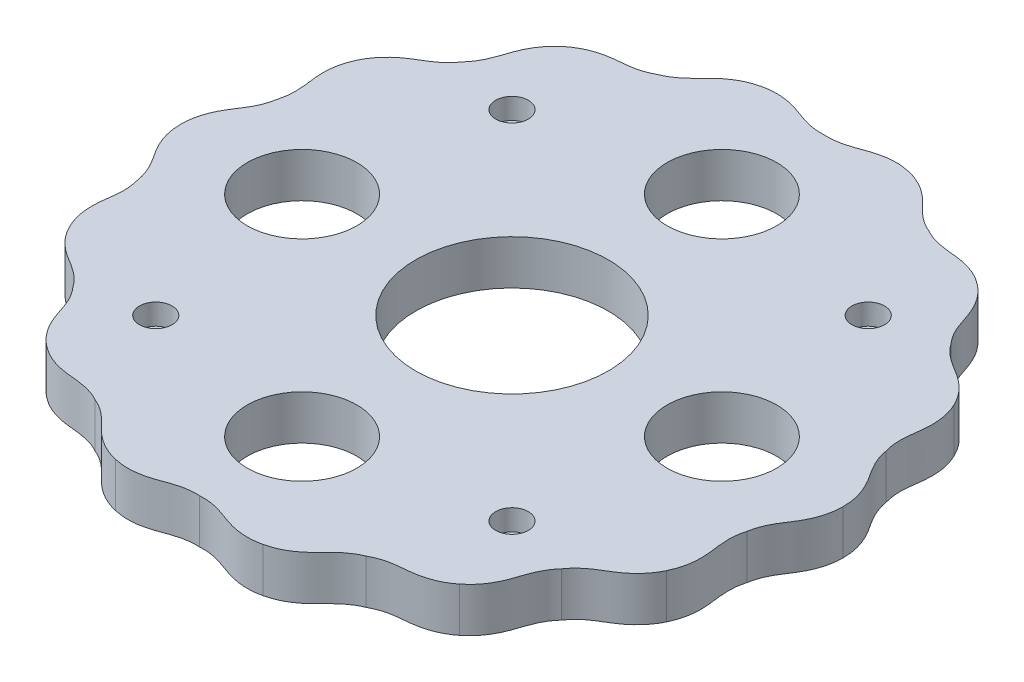
SolidWorks part; units mm, degrees
ref_plane "Front Plane" through (0, 0, 0) normal (0, 0, 1) x (1, 0, 0)
ref_plane "Top Plane" through (0, 0, 0) normal (0, 1, 0) x (1, 0, 0)
ref_plane "Right Plane" through (0, 0, 0) normal (1, 0, 0) x (0, 0, -1)
sketch "Sketch1" plane through (0, 0, 0) normal (0, 1, 0) x (1, 0, 0)
  line L0 (0, 0) -> (37.5, 0) construction
  line L1 (0, 0) -> (37.4807, 1.2019) construction
  line L2 (0, 0) -> (37.423, 2.4026) construction
  line L3 (0, 0) -> (37.3267, 3.6009) construction
  line L4 (0, 0) -> (37.1921, 4.7954) construction
  line L5 (0, 0) -> (37.0193, 5.985) construction
  line L6 (0, 0) -> (36.8085, 7.1684) construction
  line L7 (0, 0) -> (36.5598, 8.3445) construction
  line L8 (0, 0) -> (36.2736, 9.512) construction
  line L9 (0, 0) -> (35.95, 10.6698) construction
  line L10 (0, 0) -> (35.5896, 11.8166) construction
  line L11 (0, 0) -> (35.1926, 12.9512) construction
  line L12 (0, 0) -> (34.7594, 14.0725) construction
  line L13 (0, 0) -> (34.2905, 15.1794) construction
  line L14 (0, 0) -> (33.7863, 16.2706) construction
  line L15 (37.5, 0) -> (38.5, 0) construction
  line L16 (37.4807, 1.2019) -> (38.3521, 1.6927) construction
  line L17 (37.423, 2.4026) -> (37.9413, 3.2578) construction
  line L18 (37.3267, 3.6009) -> (37.3588, 4.6003) construction
  line L19 (37.1921, 4.7954) -> (36.7296, 5.682) construction
  line L20 (37.0193, 5.985) -> (36.1812, 6.5305) construction
  line L21 (36.8085, 7.1684) -> (35.8105, 7.2325) construction
  line L22 (36.5598, 8.3445) -> (35.5849, 8.122) construction
  line L23 (37, 0.0019) -> (37, 0)
  line L24 (33.3367, 16.052) -> (33.3358, 16.0537)
  line L25 (37, -0.0019) -> (37, 0)
  line L26 (33.3367, -16.052) -> (33.3358, -16.0537)
  line L27 (33.335, -16.0554) -> (33.3358, -16.0537)
  line L28 (23.0706, -28.9266) -> (23.0691, -28.9278)
  line L29 (23.0677, -28.9289) -> (23.0691, -28.9278)
  line L30 (8.2351, -36.0719) -> (8.2333, -36.0723)
  line L31 (8.2315, -36.0727) -> (8.2333, -36.0723)
  line L32 (-8.2315, -36.0727) -> (-8.2333, -36.0723)
  line L33 (-8.2351, -36.0719) -> (-8.2333, -36.0723)
  line L34 (-23.0677, -28.9289) -> (-23.0691, -28.9278)
  line L35 (-23.0706, -28.9266) -> (-23.0691, -28.9278)
  line L36 (-33.335, -16.0554) -> (-33.3358, -16.0537)
  line L37 (-33.3367, -16.052) -> (-33.3358, -16.0537)
  line L38 (-37, -0.0019) -> (-37, 0)
  line L39 (-37, 0.0019) -> (-37, 0)
  line L40 (-33.3367, 16.052) -> (-33.3358, 16.0537)
  line L41 (-33.335, 16.0554) -> (-33.3358, 16.0537)
  line L42 (-23.0706, 28.9266) -> (-23.0691, 28.9278)
  line L43 (-23.0677, 28.9289) -> (-23.0691, 28.9278)
  line L44 (-8.2351, 36.0719) -> (-8.2333, 36.0723)
  line L45 (-8.2315, 36.0727) -> (-8.2333, 36.0723)
  line L46 (8.2315, 36.0727) -> (8.2333, 36.0723)
  line L47 (8.2351, 36.0719) -> (8.2333, 36.0723)
  line L48 (23.0677, 28.9289) -> (23.0691, 28.9278)
  line L49 (23.0706, 28.9266) -> (23.0691, 28.9278)
  line L50 (33.335, 16.0554) -> (33.3358, 16.0537)
  line L51 (35.5, 0.0037) -> (35.5, 0)
  line L52 (31.986, 15.3995) -> (31.9844, 15.4029)
  line L53 (35.5, -0.0037) -> (35.5, 0)
  line L54 (31.986, -15.3995) -> (31.9844, -15.4029)
  line L55 (31.9828, -15.4062) -> (31.9844, -15.4029)
  line L56 (22.1368, -27.7527) -> (22.1339, -27.755)
  line L57 (22.131, -27.7573) -> (22.1339, -27.755)
  line L58 (7.9031, -34.6091) -> (7.8995, -34.6099)
  line L59 (7.8959, -34.6108) -> (7.8995, -34.6099)
  line L60 (-7.8959, -34.6108) -> (-7.8995, -34.6099)
  line L61 (-7.9031, -34.6091) -> (-7.8995, -34.6099)
  line L62 (-22.131, -27.7573) -> (-22.1339, -27.755)
  line L63 (-22.1368, -27.7527) -> (-22.1339, -27.755)
  line L64 (-31.9828, -15.4062) -> (-31.9844, -15.4029)
  line L65 (-31.986, -15.3995) -> (-31.9844, -15.4029)
  line L66 (-35.5, -0.0037) -> (-35.5, 0)
  line L67 (-35.5, 0.0037) -> (-35.5, 0)
  line L68 (-31.986, 15.3995) -> (-31.9844, 15.4029)
  line L69 (-31.9828, 15.4062) -> (-31.9844, 15.4029)
  line L70 (-22.1368, 27.7527) -> (-22.1339, 27.755)
  line L71 (-22.131, 27.7573) -> (-22.1339, 27.755)
  line L72 (-7.9031, 34.6091) -> (-7.8995, 34.6099)
  line L73 (-7.8959, 34.6108) -> (-7.8995, 34.6099)
  line L74 (7.8959, 34.6108) -> (7.8995, 34.6099)
  line L75 (7.9031, 34.6091) -> (7.8995, 34.6099)
  line L76 (22.131, 27.7573) -> (22.1339, 27.755)
  line L77 (22.1368, 27.7527) -> (22.1339, 27.755)
  line L78 (31.9828, 15.4062) -> (31.9844, 15.4029)
  circle A0 centre (0, 0) radius 35 construction
  circle A1 centre (37.5, 0) radius 2.5 construction
  circle A2 centre (0, 0) radius 37.5 construction
  spline S0 degree 3 poles (35.5849, 8.122) (35.6266, 7.5364) (36.0345, 6.7125) (36.7836, 5.6218) (37.4152, 4.5501) (38.2239, 2.702) (38.5014, 1.1074) (38.5, 0) knots 0 0 0 0 0.195516 0.310928 0.453873 0.621058 1 1 1 1
  spline S1 degree 3 poles (35.5849, 8.122) (35.3683, 8.6678) (35.3784, 9.5871) (35.5801, 10.8948) (35.6841, 12.1344) (35.611, 14.1503) (35.169, 15.7074) (34.6873, 16.7045) knots 0 0 0 0 0.195516 0.310928 0.453873 0.621058 1 1 1 1
  spline S2 degree 1 poles (34.1119, 7.7858) (33.3367, 16.052) knots 0 0 1 1 construction
  spline S3 degree 1 poles (34.1119, 7.7858) (37, 0.0019) knots 0 0 1 1 construction
  spline S4 degree 3 poles (33.3367, 16.052) (33.6005, 15.5058) (33.9037, 14.6401) (34.1146, 13.4372) (34.174, 12.5211) (34.1413, 11.5771) (34.0239, 10.6392) (33.8823, 9.6155) (33.9055, 8.625) (34.0243, 8.0514) (34.1119, 7.7858) knots 0.015853 0.015853 0.015853 0.015853 0.26189 0.384908 0.507927 0.630945 0.753963 0.876982 0.938491 1 1 1 1
  spline S5 degree 3 poles (34.1119, 7.7858) (34.1483, 7.5085) (34.2901, 6.9402) (34.6989, 6.0377) (35.2706, 5.1769) (35.7834, 4.3828) (36.2224, 3.5464) (36.5664, 2.6953) (36.8983, 1.52) (37.0008, 0.6085) (37, 0.0019) knots 0.015853 0.015853 0.015853 0.015853 0.077362 0.138872 0.26189 0.384908 0.507927 0.630945 0.753963 1 1 1 1
  spline S6 degree 3 poles (37, -0.0019) (37.0008, -0.6085) (36.8983, -1.52) (36.5664, -2.6953) (36.2224, -3.5464) (35.7834, -4.3828) (35.2706, -5.1769) (34.6989, -6.0377) (34.2901, -6.9402) (34.1483, -7.5085) (34.1119, -7.7858) knots 0.015853 0.015853 0.015853 0.015853 0.26189 0.384908 0.507927 0.630945 0.753963 0.876982 0.938491 1 1 1 1
  spline S7 degree 3 poles (34.1119, -7.7858) (34.0243, -8.0514) (33.9055, -8.625) (33.8823, -9.6155) (34.0239, -10.6392) (34.1413, -11.5771) (34.174, -12.5211) (34.1146, -13.4372) (33.9037, -14.6401) (33.6005, -15.5058) (33.3367, -16.052) knots 0.015853 0.015853 0.015853 0.015853 0.077362 0.138872 0.26189 0.384908 0.507927 0.630945 0.753963 1 1 1 1
  spline S8 degree 3 poles (33.335, -16.0554) (33.0725, -16.6022) (32.5847, -17.3791) (31.7758, -18.2939) (31.0965, -18.9115) (30.3381, -19.4746) (29.5316, -19.9675) (28.6429, -20.4951) (27.8831, -21.1308) (27.5087, -21.5813) (27.3556, -21.8154) knots 0.015853 0.015853 0.015853 0.015853 0.26189 0.384908 0.507927 0.630945 0.753963 0.876982 0.938491 1 1 1 1
  spline S9 degree 3 poles (27.3556, -21.8154) (27.1615, -22.0167) (26.8056, -22.4819) (26.3549, -23.3642) (26.0383, -24.348) (25.7371, -25.2439) (25.357, -26.1087) (24.906, -26.9083) (24.1941, -27.9005) (23.5453, -28.549) (23.0706, -28.9266) knots 0.015853 0.015853 0.015853 0.015853 0.077362 0.138872 0.26189 0.384908 0.507927 0.630945 0.753963 1 1 1 1
  spline S10 degree 3 poles (23.0677, -28.9289) (22.5939, -29.3077) (21.8173, -29.796) (20.6915, -30.2693) (19.8116, -30.531) (18.884, -30.7092) (17.9435, -30.8034) (16.9139, -30.8931) (15.9535, -31.1362) (15.4207, -31.3797) (15.1812, -31.5241) knots 0.015853 0.015853 0.015853 0.015853 0.26189 0.384908 0.507927 0.630945 0.753963 0.876982 0.938491 1 1 1 1
  spline S11 degree 3 poles (15.1812, -31.5241) (14.919, -31.6213) (14.3964, -31.886) (13.6076, -32.4854) (12.8955, -33.2344) (12.2354, -33.9109) (11.5177, -34.5251) (10.7645, -35.0499) (9.6926, -35.6349) (8.8266, -35.9377) (8.2351, -36.0719) knots 0.015853 0.015853 0.015853 0.015853 0.077362 0.138872 0.26189 0.384908 0.507927 0.630945 0.753963 1 1 1 1
  spline S12 degree 3 poles (8.2315, -36.0727) (7.6402, -36.2085) (6.7287, -36.3114) (5.5091, -36.2494) (4.6028, -36.1034) (3.6897, -35.8614) (2.8014, -35.5383) (1.8349, -35.1724) (0.8641, -34.9747) (0.2785, -34.9629) (0, -34.9891) knots 0.015853 0.015853 0.015853 0.015853 0.26189 0.384908 0.507927 0.630945 0.753963 0.876982 0.938491 1 1 1 1
  spline S13 degree 3 poles (0, -34.9891) (-0.2785, -34.9629) (-0.8641, -34.9747) (-1.8349, -35.1724) (-2.8014, -35.5383) (-3.6897, -35.8614) (-4.6028, -36.1034) (-5.5091, -36.2494) (-6.7287, -36.3114) (-7.6402, -36.2085) (-8.2315, -36.0727) knots 0.015853 0.015853 0.015853 0.015853 0.077362 0.138872 0.26189 0.384908 0.507927 0.630945 0.753963 1 1 1 1
  spline S14 degree 3 poles (-8.2351, -36.0719) (-8.8266, -35.9377) (-9.6926, -35.6349) (-10.7645, -35.0499) (-11.5177, -34.5251) (-12.2354, -33.9109) (-12.8955, -33.2344) (-13.6076, -32.4854) (-14.3964, -31.886) (-14.919, -31.6213) (-15.1812, -31.5241) knots 0.015853 0.015853 0.015853 0.015853 0.26189 0.384908 0.507927 0.630945 0.753963 0.876982 0.938491 1 1 1 1
  spline S15 degree 3 poles (-15.1812, -31.5241) (-15.4207, -31.3797) (-15.9535, -31.1362) (-16.9139, -30.8931) (-17.9435, -30.8034) (-18.884, -30.7092) (-19.8116, -30.531) (-20.6915, -30.2693) (-21.8173, -29.796) (-22.5939, -29.3077) (-23.0677, -28.9289) knots 0.015853 0.015853 0.015853 0.015853 0.077362 0.138872 0.26189 0.384908 0.507927 0.630945 0.753963 1 1 1 1
  spline S16 degree 3 poles (-23.0706, -28.9266) (-23.5453, -28.549) (-24.1941, -27.9005) (-24.906, -26.9083) (-25.357, -26.1087) (-25.7371, -25.2439) (-26.0383, -24.348) (-26.3549, -23.3642) (-26.8056, -22.4819) (-27.1615, -22.0167) (-27.3556, -21.8154) knots 0.015853 0.015853 0.015853 0.015853 0.26189 0.384908 0.507927 0.630945 0.753963 0.876982 0.938491 1 1 1 1
  spline S17 degree 3 poles (-27.3556, -21.8154) (-27.5087, -21.5813) (-27.8831, -21.1308) (-28.6429, -20.4951) (-29.5316, -19.9675) (-30.3381, -19.4746) (-31.0965, -18.9115) (-31.7758, -18.2939) (-32.5847, -17.3791) (-33.0725, -16.6022) (-33.335, -16.0554) knots 0.015853 0.015853 0.015853 0.015853 0.077362 0.138872 0.26189 0.384908 0.507927 0.630945 0.753963 1 1 1 1
  spline S18 degree 3 poles (-33.3367, -16.052) (-33.6005, -15.5058) (-33.9037, -14.6401) (-34.1146, -13.4372) (-34.174, -12.5211) (-34.1413, -11.5771) (-34.0239, -10.6392) (-33.8823, -9.6155) (-33.9055, -8.625) (-34.0243, -8.0514) (-34.1119, -7.7858) knots 0.015853 0.015853 0.015853 0.015853 0.26189 0.384908 0.507927 0.630945 0.753963 0.876982 0.938491 1 1 1 1
  spline S19 degree 3 poles (-34.1119, -7.7858) (-34.1483, -7.5085) (-34.2901, -6.9402) (-34.6989, -6.0377) (-35.2706, -5.1769) (-35.7834, -4.3828) (-36.2224, -3.5464) (-36.5664, -2.6953) (-36.8983, -1.52) (-37.0008, -0.6085) (-37, -0.0019) knots 0.015853 0.015853 0.015853 0.015853 0.077362 0.138872 0.26189 0.384908 0.507927 0.630945 0.753963 1 1 1 1
  spline S20 degree 3 poles (-37, 0.0019) (-37.0008, 0.6085) (-36.8983, 1.52) (-36.5664, 2.6953) (-36.2224, 3.5464) (-35.7834, 4.3828) (-35.2706, 5.1769) (-34.6989, 6.0377) (-34.2901, 6.9402) (-34.1483, 7.5085) (-34.1119, 7.7858) knots 0.015853 0.015853 0.015853 0.015853 0.26189 0.384908 0.507927 0.630945 0.753963 0.876982 0.938491 1 1 1 1
  spline S21 degree 3 poles (-34.1119, 7.7858) (-34.0243, 8.0514) (-33.9055, 8.625) (-33.8823, 9.6155) (-34.0239, 10.6392) (-34.1413, 11.5771) (-34.174, 12.5211) (-34.1146, 13.4372) (-33.9037, 14.6401) (-33.6005, 15.5058) (-33.3367, 16.052) knots 0.015853 0.015853 0.015853 0.015853 0.077362 0.138872 0.26189 0.384908 0.507927 0.630945 0.753963 1 1 1 1
  spline S22 degree 3 poles (-33.335, 16.0554) (-33.0725, 16.6022) (-32.5847, 17.3791) (-31.7758, 18.2939) (-31.0965, 18.9115) (-30.3381, 19.4746) (-29.5316, 19.9675) (-28.6429, 20.4951) (-27.8831, 21.1308) (-27.5087, 21.5813) (-27.3556, 21.8154) knots 0.015853 0.015853 0.015853 0.015853 0.26189 0.384908 0.507927 0.630945 0.753963 0.876982 0.938491 1 1 1 1
  spline S23 degree 3 poles (-27.3556, 21.8154) (-27.1615, 22.0167) (-26.8056, 22.4819) (-26.3549, 23.3642) (-26.0383, 24.348) (-25.7371, 25.2439) (-25.357, 26.1087) (-24.906, 26.9083) (-24.1941, 27.9005) (-23.5453, 28.549) (-23.0706, 28.9266) knots 0.015853 0.015853 0.015853 0.015853 0.077362 0.138872 0.26189 0.384908 0.507927 0.630945 0.753963 1 1 1 1
  spline S24 degree 3 poles (-23.0677, 28.9289) (-22.5939, 29.3077) (-21.8173, 29.796) (-20.6915, 30.2693) (-19.8116, 30.531) (-18.884, 30.7092) (-17.9435, 30.8034) (-16.9139, 30.8931) (-15.9535, 31.1362) (-15.4207, 31.3797) (-15.1812, 31.5241) knots 0.015853 0.015853 0.015853 0.015853 0.26189 0.384908 0.507927 0.630945 0.753963 0.876982 0.938491 1 1 1 1
  spline S25 degree 3 poles (-15.1812, 31.5241) (-14.919, 31.6213) (-14.3964, 31.886) (-13.6076, 32.4854) (-12.8955, 33.2344) (-12.2354, 33.9109) (-11.5177, 34.5251) (-10.7645, 35.0499) (-9.6926, 35.6349) (-8.8266, 35.9377) (-8.2351, 36.0719) knots 0.015853 0.015853 0.015853 0.015853 0.077362 0.138872 0.26189 0.384908 0.507927 0.630945 0.753963 1 1 1 1
  spline S26 degree 3 poles (-8.2315, 36.0727) (-7.6402, 36.2085) (-6.7287, 36.3114) (-5.5091, 36.2494) (-4.6028, 36.1034) (-3.6897, 35.8614) (-2.8014, 35.5383) (-1.8349, 35.1724) (-0.8641, 34.9747) (-0.2785, 34.9629) (0, 34.9891) knots 0.015853 0.015853 0.015853 0.015853 0.26189 0.384908 0.507927 0.630945 0.753963 0.876982 0.938491 1 1 1 1
  spline S27 degree 3 poles (0, 34.9891) (0.2785, 34.9629) (0.8641, 34.9747) (1.8349, 35.1724) (2.8014, 35.5383) (3.6897, 35.8614) (4.6028, 36.1034) (5.5091, 36.2494) (6.7287, 36.3114) (7.6402, 36.2085) (8.2315, 36.0727) knots 0.015853 0.015853 0.015853 0.015853 0.077362 0.138872 0.26189 0.384908 0.507927 0.630945 0.753963 1 1 1 1
  spline S28 degree 3 poles (8.2351, 36.0719) (8.8266, 35.9377) (9.6926, 35.6349) (10.7645, 35.0499) (11.5177, 34.5251) (12.2354, 33.9109) (12.8955, 33.2344) (13.6076, 32.4854) (14.3964, 31.886) (14.919, 31.6213) (15.1812, 31.5241) knots 0.015853 0.015853 0.015853 0.015853 0.26189 0.384908 0.507927 0.630945 0.753963 0.876982 0.938491 1 1 1 1
  spline S29 degree 3 poles (15.1812, 31.5241) (15.4207, 31.3797) (15.9535, 31.1362) (16.9139, 30.8931) (17.9435, 30.8034) (18.884, 30.7092) (19.8116, 30.531) (20.6915, 30.2693) (21.8173, 29.796) (22.5939, 29.3077) (23.0677, 28.9289) knots 0.015853 0.015853 0.015853 0.015853 0.077362 0.138872 0.26189 0.384908 0.507927 0.630945 0.753963 1 1 1 1
  spline S30 degree 3 poles (23.0706, 28.9266) (23.5453, 28.549) (24.1941, 27.9005) (24.906, 26.9083) (25.357, 26.1087) (25.7371, 25.2439) (26.0383, 24.348) (26.3549, 23.3642) (26.8056, 22.4819) (27.1615, 22.0167) (27.3556, 21.8154) knots 0.015853 0.015853 0.015853 0.015853 0.26189 0.384908 0.507927 0.630945 0.753963 0.876982 0.938491 1 1 1 1
  spline S31 degree 3 poles (27.3556, 21.8154) (27.5087, 21.5813) (27.8831, 21.1308) (28.6429, 20.4951) (29.5316, 19.9675) (30.3381, 19.4746) (31.0965, 18.9115) (31.7758, 18.2939) (32.5847, 17.3791) (33.0725, 16.6022) (33.335, 16.0554) knots 0.015853 0.015853 0.015853 0.015853 0.077362 0.138872 0.26189 0.384908 0.507927 0.630945 0.753963 1 1 1 1
  spline S32 degree 1 poles (32.6448, 7.451) (35.5, 0.0037) knots 0 0 1 1 construction
  spline S33 degree 1 poles (32.6448, 7.451) (31.986, 15.3995) knots 0 0 1 1 construction
  spline S34 degree 3 poles (35.5, 0.0037) (35.5006, 0.4959) (35.4183, 1.2336) (35.1496, 2.1927) (34.8707, 2.8896) (34.4997, 3.6015) (34.1394, 4.1652) (33.6939, 4.8394) (33.3068, 5.4873) (32.9751, 6.1975) (32.758, 6.8733) (32.6748, 7.2607) (32.6448, 7.451) knots 0.023011 0.023011 0.023011 0.023011 0.267258 0.389382 0.511505 0.633629 0.755753 0.816814 0.877876 0.938938 0.969469 1 1 1 1
  spline S35 degree 3 poles (32.6448, 7.451) (32.5893, 7.6354) (32.4961, 8.0206) (32.3985, 8.7236) (32.3893, 9.5074) (32.4569, 10.2591) (32.5657, 11.0598) (32.6458, 11.724) (32.6712, 12.5264) (32.6201, 13.2752) (32.446, 14.256) (32.2001, 14.9563) (31.986, 15.3995) knots 0.023011 0.023011 0.023011 0.023011 0.053542 0.084072 0.145134 0.206196 0.267258 0.389382 0.511505 0.633629 0.755753 1 1 1 1
  spline S36 degree 3 poles (32.6448, -7.451) (32.6748, -7.2607) (32.758, -6.8733) (32.9751, -6.1975) (33.3068, -5.4873) (33.6939, -4.8394) (34.1394, -4.1652) (34.4997, -3.6015) (34.8707, -2.8896) (35.1496, -2.1927) (35.4183, -1.2336) (35.5006, -0.4959) (35.5, -0.0037) knots 0.023011 0.023011 0.023011 0.023011 0.053542 0.084072 0.145134 0.206196 0.267258 0.389382 0.511505 0.633629 0.755753 1 1 1 1
  spline S37 degree 3 poles (31.986, -15.3995) (32.2001, -14.9563) (32.446, -14.256) (32.6201, -13.2752) (32.6712, -12.5264) (32.6458, -11.724) (32.5657, -11.0598) (32.4569, -10.2591) (32.3893, -9.5074) (32.3985, -8.7236) (32.4961, -8.0206) (32.5893, -7.6354) (32.6448, -7.451) knots 0.023011 0.023011 0.023011 0.023011 0.267258 0.389382 0.511505 0.633629 0.755753 0.816814 0.877876 0.938938 0.969469 1 1 1 1
  spline S38 degree 3 poles (26.1791, -20.8771) (26.2887, -20.7187) (26.5317, -20.4057) (27.0205, -19.8911) (27.6275, -19.3952) (28.2574, -18.9793) (28.9513, -18.5652) (29.5206, -18.2137) (30.1637, -17.7333) (30.7173, -17.2264) (31.3755, -16.4789) (31.7698, -15.8499) (31.9828, -15.4062) knots 0.023011 0.023011 0.023011 0.023011 0.053542 0.084072 0.145134 0.206196 0.267258 0.389382 0.511505 0.633629 0.755753 1 1 1 1
  spline S39 degree 3 poles (22.1368, -27.7527) (22.522, -27.4463) (23.0474, -26.922) (23.6297, -26.1139) (24.0007, -25.4614) (24.326, -24.7275) (24.542, -24.0943) (24.7914, -23.3257) (25.0566, -22.619) (25.405, -21.9169) (25.798, -21.3258) (26.0491, -21.0192) (26.1791, -20.8771) knots 0.023011 0.023011 0.023011 0.023011 0.267258 0.389382 0.511505 0.633629 0.755753 0.816814 0.877876 0.938938 0.969469 1 1 1 1
  spline S40 degree 3 poles (14.5283, -30.1683) (14.6957, -30.0732) (15.0505, -29.8966) (15.7143, -29.645) (16.4763, -29.4616) (17.2242, -29.3602) (18.0291, -29.2882) (18.6945, -29.2185) (19.4823, -29.0647) (20.201, -28.8482) (21.1184, -28.4603) (21.7465, -28.0647) (22.131, -27.7573) knots 0.023011 0.023011 0.023011 0.023011 0.053542 0.084072 0.145134 0.206196 0.267258 0.389382 0.511505 0.633629 0.755753 1 1 1 1
  spline S41 degree 3 poles (7.9031, -34.6091) (8.3831, -34.5002) (9.084, -34.2557) (9.9593, -33.7804) (10.5766, -33.3534) (11.1881, -32.8334) (11.6575, -32.3566) (12.2156, -31.7723) (12.7612, -31.2507) (13.3797, -30.7693) (13.9903, -30.4072) (14.3495, -30.2399) (14.5283, -30.1683) knots 0.023011 0.023011 0.023011 0.023011 0.267258 0.389382 0.511505 0.633629 0.755753 0.816814 0.877876 0.938938 0.969469 1 1 1 1
  spline S42 degree 3 poles (0, -33.4843) (0.1922, -33.4712) (0.5884, -33.4661) (1.2956, -33.5274) (2.0617, -33.6928) (2.7796, -33.926) (3.536, -34.2103) (4.1657, -34.4362) (4.9423, -34.6394) (5.6838, -34.7562) (6.6786, -34.8048) (7.4161, -34.7209) (7.8959, -34.6108) knots 0.023011 0.023011 0.023011 0.023011 0.053542 0.084072 0.145134 0.206196 0.267258 0.389382 0.511505 0.633629 0.755753 1 1 1 1
  spline S43 degree 3 poles (-7.8959, -34.6108) (-7.4161, -34.7209) (-6.6786, -34.8048) (-5.6838, -34.7562) (-4.9423, -34.6394) (-4.1657, -34.4362) (-3.536, -34.2103) (-2.7796, -33.926) (-2.0617, -33.6928) (-1.2956, -33.5274) (-0.5884, -33.4661) (-0.1922, -33.4712) (0, -33.4843) knots 0.023011 0.023011 0.023011 0.023011 0.267258 0.389382 0.511505 0.633629 0.755753 0.816814 0.877876 0.938938 0.969469 1 1 1 1
  spline S44 degree 3 poles (-14.5283, -30.1683) (-14.3495, -30.2399) (-13.9903, -30.4072) (-13.3797, -30.7693) (-12.7612, -31.2507) (-12.2156, -31.7723) (-11.6575, -32.3566) (-11.1881, -32.8334) (-10.5766, -33.3534) (-9.9593, -33.7804) (-9.084, -34.2557) (-8.3831, -34.5002) (-7.9031, -34.6091) knots 0.023011 0.023011 0.023011 0.023011 0.053542 0.084072 0.145134 0.206196 0.267258 0.389382 0.511505 0.633629 0.755753 1 1 1 1
  spline S45 degree 3 poles (-22.131, -27.7573) (-21.7465, -28.0647) (-21.1184, -28.4603) (-20.201, -28.8482) (-19.4823, -29.0647) (-18.6945, -29.2185) (-18.0291, -29.2882) (-17.2242, -29.3602) (-16.4763, -29.4616) (-15.7143, -29.645) (-15.0505, -29.8966) (-14.6957, -30.0732) (-14.5283, -30.1683) knots 0.023011 0.023011 0.023011 0.023011 0.267258 0.389382 0.511505 0.633629 0.755753 0.816814 0.877876 0.938938 0.969469 1 1 1 1
  spline S46 degree 3 poles (-26.1791, -20.8771) (-26.0491, -21.0192) (-25.798, -21.3258) (-25.405, -21.9169) (-25.0566, -22.619) (-24.7914, -23.3257) (-24.542, -24.0943) (-24.326, -24.7275) (-24.0007, -25.4614) (-23.6297, -26.1139) (-23.0474, -26.922) (-22.522, -27.4463) (-22.1368, -27.7527) knots 0.023011 0.023011 0.023011 0.023011 0.053542 0.084072 0.145134 0.206196 0.267258 0.389382 0.511505 0.633629 0.755753 1 1 1 1
  spline S47 degree 3 poles (-31.9828, -15.4062) (-31.7698, -15.8499) (-31.3755, -16.4789) (-30.7173, -17.2264) (-30.1637, -17.7333) (-29.5206, -18.2137) (-28.9513, -18.5652) (-28.2574, -18.9793) (-27.6275, -19.3952) (-27.0205, -19.8911) (-26.5317, -20.4057) (-26.2887, -20.7187) (-26.1791, -20.8771) knots 0.023011 0.023011 0.023011 0.023011 0.267258 0.389382 0.511505 0.633629 0.755753 0.816814 0.877876 0.938938 0.969469 1 1 1 1
  spline S48 degree 3 poles (-32.6448, -7.451) (-32.5893, -7.6354) (-32.4961, -8.0206) (-32.3985, -8.7236) (-32.3893, -9.5074) (-32.4569, -10.2591) (-32.5657, -11.0598) (-32.6458, -11.724) (-32.6712, -12.5264) (-32.6201, -13.2752) (-32.446, -14.256) (-32.2001, -14.9563) (-31.986, -15.3995) knots 0.023011 0.023011 0.023011 0.023011 0.053542 0.084072 0.145134 0.206196 0.267258 0.389382 0.511505 0.633629 0.755753 1 1 1 1
  spline S49 degree 3 poles (-35.5, -0.0037) (-35.5006, -0.4959) (-35.4183, -1.2336) (-35.1496, -2.1927) (-34.8707, -2.8896) (-34.4997, -3.6015) (-34.1394, -4.1652) (-33.6939, -4.8394) (-33.3068, -5.4873) (-32.9751, -6.1975) (-32.758, -6.8733) (-32.6748, -7.2607) (-32.6448, -7.451) knots 0.023011 0.023011 0.023011 0.023011 0.267258 0.389382 0.511505 0.633629 0.755753 0.816814 0.877876 0.938938 0.969469 1 1 1 1
  spline S50 degree 3 poles (-32.6448, 7.451) (-32.6748, 7.2607) (-32.758, 6.8733) (-32.9751, 6.1975) (-33.3068, 5.4873) (-33.6939, 4.8394) (-34.1394, 4.1652) (-34.4997, 3.6015) (-34.8707, 2.8896) (-35.1496, 2.1927) (-35.4183, 1.2336) (-35.5006, 0.4959) (-35.5, 0.0037) knots 0.023011 0.023011 0.023011 0.023011 0.053542 0.084072 0.145134 0.206196 0.267258 0.389382 0.511505 0.633629 0.755753 1 1 1 1
  spline S51 degree 3 poles (-31.986, 15.3995) (-32.2001, 14.9563) (-32.446, 14.256) (-32.6201, 13.2752) (-32.6712, 12.5264) (-32.6458, 11.724) (-32.5657, 11.0598) (-32.4569, 10.2591) (-32.3893, 9.5074) (-32.3985, 8.7236) (-32.4961, 8.0206) (-32.5893, 7.6354) (-32.6448, 7.451) knots 0.023011 0.023011 0.023011 0.023011 0.267258 0.389382 0.511505 0.633629 0.755753 0.816814 0.877876 0.938938 0.969469 1 1 1 1
  spline S52 degree 3 poles (-26.1791, 20.8771) (-26.2887, 20.7187) (-26.5317, 20.4057) (-27.0205, 19.8911) (-27.6275, 19.3952) (-28.2574, 18.9793) (-28.9513, 18.5652) (-29.5206, 18.2137) (-30.1637, 17.7333) (-30.7173, 17.2264) (-31.3755, 16.4789) (-31.7698, 15.8499) (-31.9828, 15.4062) knots 0.023011 0.023011 0.023011 0.023011 0.053542 0.084072 0.145134 0.206196 0.267258 0.389382 0.511505 0.633629 0.755753 1 1 1 1
  spline S53 degree 3 poles (-22.1368, 27.7527) (-22.522, 27.4463) (-23.0474, 26.922) (-23.6297, 26.1139) (-24.0007, 25.4614) (-24.326, 24.7275) (-24.542, 24.0943) (-24.7914, 23.3257) (-25.0566, 22.619) (-25.405, 21.9169) (-25.798, 21.3258) (-26.0491, 21.0192) (-26.1791, 20.8771) knots 0.023011 0.023011 0.023011 0.023011 0.267258 0.389382 0.511505 0.633629 0.755753 0.816814 0.877876 0.938938 0.969469 1 1 1 1
  spline S54 degree 3 poles (-14.5283, 30.1683) (-14.6957, 30.0732) (-15.0505, 29.8966) (-15.7143, 29.645) (-16.4763, 29.4616) (-17.2242, 29.3602) (-18.0291, 29.2882) (-18.6945, 29.2185) (-19.4823, 29.0647) (-20.201, 28.8482) (-21.1184, 28.4603) (-21.7465, 28.0647) (-22.131, 27.7573) knots 0.023011 0.023011 0.023011 0.023011 0.053542 0.084072 0.145134 0.206196 0.267258 0.389382 0.511505 0.633629 0.755753 1 1 1 1
  spline S55 degree 3 poles (-7.9031, 34.6091) (-8.3831, 34.5002) (-9.084, 34.2557) (-9.9593, 33.7804) (-10.5766, 33.3534) (-11.1881, 32.8334) (-11.6575, 32.3566) (-12.2156, 31.7723) (-12.7612, 31.2507) (-13.3797, 30.7693) (-13.9903, 30.4072) (-14.3495, 30.2399) (-14.5283, 30.1683) knots 0.023011 0.023011 0.023011 0.023011 0.267258 0.389382 0.511505 0.633629 0.755753 0.816814 0.877876 0.938938 0.969469 1 1 1 1
  spline S56 degree 3 poles (0, 33.4843) (-0.1922, 33.4712) (-0.5884, 33.4661) (-1.2956, 33.5274) (-2.0617, 33.6928) (-2.7796, 33.926) (-3.536, 34.2103) (-4.1657, 34.4362) (-4.9423, 34.6394) (-5.6838, 34.7562) (-6.6786, 34.8048) (-7.4161, 34.7209) (-7.8959, 34.6108) knots 0.023011 0.023011 0.023011 0.023011 0.053542 0.084072 0.145134 0.206196 0.267258 0.389382 0.511505 0.633629 0.755753 1 1 1 1
  spline S57 degree 3 poles (7.8959, 34.6108) (7.4161, 34.7209) (6.6786, 34.8048) (5.6838, 34.7562) (4.9423, 34.6394) (4.1657, 34.4362) (3.536, 34.2103) (2.7796, 33.926) (2.0617, 33.6928) (1.2956, 33.5274) (0.5884, 33.4661) (0.1922, 33.4712) (0, 33.4843) knots 0.023011 0.023011 0.023011 0.023011 0.267258 0.389382 0.511505 0.633629 0.755753 0.816814 0.877876 0.938938 0.969469 1 1 1 1
  spline S58 degree 3 poles (14.5283, 30.1683) (14.3495, 30.2399) (13.9903, 30.4072) (13.3797, 30.7693) (12.7612, 31.2507) (12.2156, 31.7723) (11.6575, 32.3566) (11.1881, 32.8334) (10.5766, 33.3534) (9.9593, 33.7804) (9.084, 34.2557) (8.3831, 34.5002) (7.9031, 34.6091) knots 0.023011 0.023011 0.023011 0.023011 0.053542 0.084072 0.145134 0.206196 0.267258 0.389382 0.511505 0.633629 0.755753 1 1 1 1
  spline S59 degree 3 poles (22.131, 27.7573) (21.7465, 28.0647) (21.1184, 28.4603) (20.201, 28.8482) (19.4823, 29.0647) (18.6945, 29.2185) (18.0291, 29.2882) (17.2242, 29.3602) (16.4763, 29.4616) (15.7143, 29.645) (15.0505, 29.8966) (14.6957, 30.0732) (14.5283, 30.1683) knots 0.023011 0.023011 0.023011 0.023011 0.267258 0.389382 0.511505 0.633629 0.755753 0.816814 0.877876 0.938938 0.969469 1 1 1 1
  spline S60 degree 3 poles (26.1791, 20.8771) (26.0491, 21.0192) (25.798, 21.3258) (25.405, 21.9169) (25.0566, 22.619) (24.7914, 23.3257) (24.542, 24.0943) (24.326, 24.7275) (24.0007, 25.4614) (23.6297, 26.1139) (23.0474, 26.922) (22.522, 27.4463) (22.1368, 27.7527) knots 0.023011 0.023011 0.023011 0.023011 0.053542 0.084072 0.145134 0.206196 0.267258 0.389382 0.511505 0.633629 0.755753 1 1 1 1
  spline S61 degree 3 poles (31.9828, 15.4062) (31.7698, 15.8499) (31.3755, 16.4789) (30.7173, 17.2264) (30.1637, 17.7333) (29.5206, 18.2137) (28.9513, 18.5652) (28.2574, 18.9793) (27.6275, 19.3952) (27.0205, 19.8911) (26.5317, 20.4057) (26.2887, 20.7187) (26.1791, 20.8771) knots 0.023011 0.023011 0.023011 0.023011 0.267258 0.389382 0.511505 0.633629 0.755753 0.816814 0.877876 0.938938 0.969469 1 1 1 1
  point P25 (0, 0)
  point P117 (0, 0)
  point P174 (0, 0)
  dimension "D1" = 70
  dimension "D2" = 5
  dimension "D4" = 25.714
  dimension "D5" = 1
  dimension "D7" = 180
  dimension "D8" = 207.551
  dimension "D6" = 1
  dimension "D9" = 1
  dimension "D10" = 235.102
  dimension "D11" = 1
  dimension "D12" = 1
  dimension "D13" = 1
  dimension "D14" = 1
  dimension "D15" = 1
  dimension "D16" = 262.653
  dimension "D17" = 290.204
  dimension "D18" = 317.755
  dimension "D19" = 345.306
  dimension "D20" = 1.5
  dimension "D22" = 3
  dimension "D3" = 15
  dimension "D21" = 14
  dimension "D23" = 14
extrude "Boss-Extrude3" add sketch "Sketch1" along normal blind 4.7625 contours L51 L53 S36 S37 L54 L55 S38 S39 L56 L57 S40 S41 L58 L59 S42 S43 L60 L61 S44 S45 L62 L63 S46 S47 L64 L65 S48 S49 L66 L67 S50 S51 L68 L69 S52 S53 L70 L71 S54 S55 L72 L73 S56 S57 L74 L75 S58 S59 L76 L77 S60 S61 L78 L52 S35 S34
sketch "Sketch2" plane through (0, 4.7625, 0) normal (0, 1, 0) x (1, 0, 0)
  line L0 (0, 0) -> (22.5, 0) construction
  line L1 (0, 0) -> (19.0919, 19.0919) construction
  circle A0 centre (0, 0) radius 10.3281
  circle A1 centre (22.5, 0) radius 5.875
  circle A6 centre (19.0919, 19.0919) radius 1.75
  circle A7 centre (0, -22.5) radius 5.875
  circle A8 centre (19.0919, -19.0919) radius 1.75
  circle A9 centre (-22.5, 0) radius 5.875
  circle A10 centre (-19.0919, -19.0919) radius 1.75
  circle A11 centre (0, 22.5) radius 5.875
  circle A12 centre (-19.0919, 19.0919) radius 1.75
  point P16 (0, 0)
  point P21 (0, 0)
  point P24 (0, 0)
  dimension "D3" = 11.75
  dimension "D1" = 20.6562
  dimension "D6" = 3.5
  dimension "D2" = 22.5
  dimension "D4" = 45
  dimension "D5" = 27
  dimension "D7" = 4
extrude "Cut-Extrude1" cut sketch "Sketch2" against normal blind 4.7625 contours A7 | A0 | A0 | A0 | L0 A0 | A0 L0 | A1 | A9 | A11 region at (0, 4.7625, 0) region at (22.5, 4.7625, 0) region at (0, 4.7625, 22.5) region at (-22.5, 4.7625, 0) region at (0, 4.7625, -22.5)
extrude "Cut-Extrude2" cut sketch "Sketch2<4>" against normal blind 2.2458 contours A12 | A10 | A8 | A6 region at (19.0919, 4.7625, -19.0919) region at (19.0919, 4.7625, 19.0919) region at (-19.0919, 4.7625, 19.0919) region at (-19.0919, 4.7625, -19.0919)
sketch "Sketch2<4>" plane through (0, 4.7625, 0) normal (0, 1, 0) x (1, 0, 0) same geometry as "Sketch2"
equation "\"D5@Sketch1\" = \"eccentricity\""
equation "\"D6@Sketch1\" = \"eccentricity\""
equation "\"D9@Sketch1\" = \"eccentricity\""
equation "\"D11@Sketch1\" = \"eccentricity\""
equation "\"D12@Sketch1\" = \"eccentricity\""
equation "\"D14@Sketch1\" = \"eccentricity\""
equation "\"D13@Sketch1\" = \"eccentricity\""
equation "\"D15@Sketch1\"= \"eccentricity\""
equation "\"D1@Sketch2\"=\"largeBearOD\"-\"largeBearOTight\""
equation "\"D1@Cut-Extrude2\"=\"ballBearDiam\"-(\"sheetThickness\"-1)/3"
equation "\"D1@Boss-Extrude3\"=\"sheetThickness\""
equation "\"smallBearOD\"= 14.8mm"
equation "\"smallBearID\" = 10mm"
equation "\"smallBearOTight\"= 0mm'calibrate - hold onto bottom of gearbox"
equation "\"smallBearOLoose\"= 0mm'calibrate - able to take off topHat"
equation "\"smallBearITight\" = 0mm'hold onto "
equation "\"pinCircleDiam\"= 75mm"
equation "\"pinDiam\"= 6mm"
equation "\"sheetThickness\"= 0.1875in"
equation "\"D6@Sketch2\"=\"ballBearDiam\""
equation "\"largeBearOD\"= 21mm"
equation "\"largeBearID\" = 15mm"
equation "\"largeBearOTight\"= 0.34375mm'calibrate - hold onto gears"
equation "\"largeBearITight\"= 0mm'calibrate - hold onto eccentric nut"
equation "\"ballBearDiam\"= 3.5mm"
equation "\"thrustBearingThickness\"= 5mm'measure this irl and change"
equation "\"thrustBearingID\"= 0mm'measure this irl and change"
equation "\"thrustBearingOD\"= 0mm'measure this irl and change"
equation "\"eccentricity\" = 1mm"
equation "\"D1@Cut-Extrude1\"=\"sheetThickness\""
